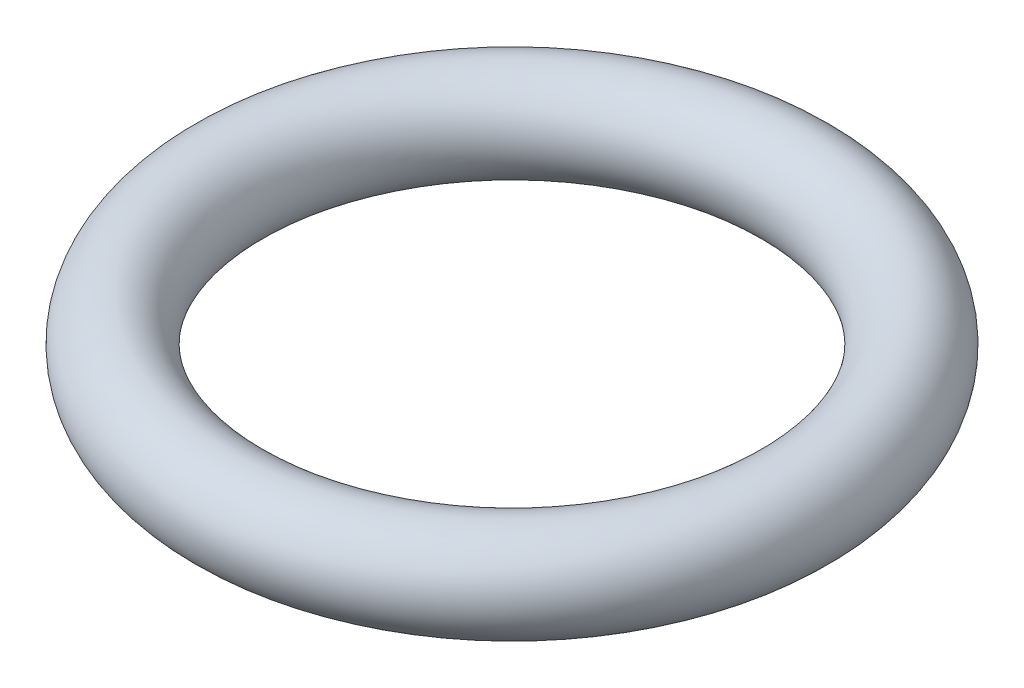
SolidWorks part; units mm, degrees
ref_plane "Front Plane" through (0, 0, 0) normal (0, 0, 1) x (1, 0, 0)
ref_plane "Top Plane" through (0, 0, 0) normal (0, 1, 0) x (1, 0, 0)
ref_plane "Right Plane" through (0, 0, 0) normal (1, 0, 0) x (0, 0, -1)
sketch "Sketch1" plane through (0, 0, 0) normal (0, 0, 1) x (1, 0, 0)
  line L0 (0, 0) -> (64.1898, 0) construction
  line L1 (0, 0) -> (0, 55.4832) construction
  circle A0 centre (152.4, 0) radius 25.4
  point P5 (177.8, 0)
  dimension "D2" = 50.8
  dimension "D1" = 177.8
revolve "Revolve1" add sketch "Sketch1" angle 360 about L1
